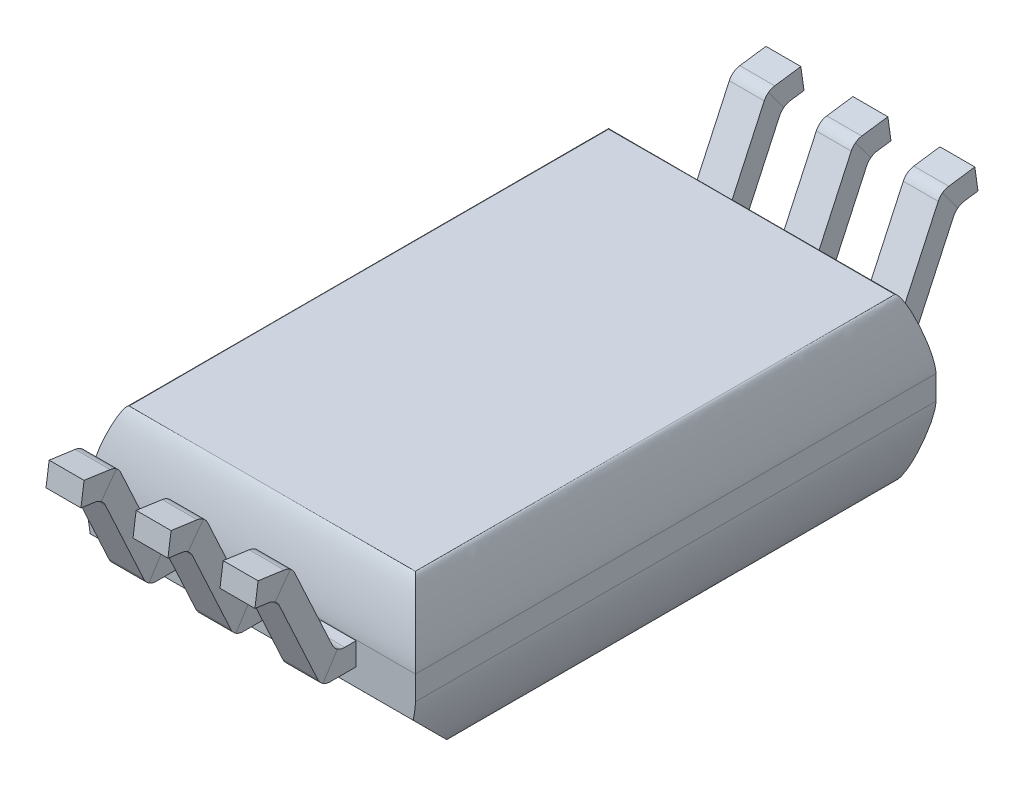
SolidWorks part; units mm, degrees
ref_plane "Front Plane" through (0, 0, 0) normal (0, 0, 1) x (1, 0, 0)
ref_plane "Top Plane" through (0, 0, 0) normal (0, 1, 0) x (1, 0, 0)
ref_plane "Right Plane" through (0, 0, 0) normal (1, 0, 0) x (0, 0, -1)
sketch "Sketch1" plane through (0, 0, 0) normal (0, 1, 0) x (1, 0, 0)
  line L1 (-2.39, -3.8) -> (2.39, -3.8)
  line L2 (-2.39, -3.8) -> (-2.39, 3.8)
  line L3 (-2.39, 3.8) -> (2.39, 3.8)
  line L4 (2.39, -3.8) -> (2.39, 3.8)
  line L5 (-2.39, -3.8) -> (2.39, 3.8) construction
  line L6 (-2.39, 3.8) -> (2.39, -3.8) construction
  point P0 (0, 0)
  dimension "D1" = 4.78
  dimension "D2" = 7.6
sketch "Sketch2" plane through (0, 0, 0) normal (1, 0, 0) x (0, 0, -1)
  line L1 (-3.8, -0.3) -> (3.8, -0.3)
  line L2 (-3.8, -0.3) -> (-3.8, -2.65)
  line L3 (-3.8, -2.65) -> (3.8, -2.65)
  line L4 (3.8, -0.3) -> (3.8, -2.65)
  line L5 (-3.8, -0.3) -> (3.8, -2.65) construction
  line L6 (-3.8, -2.65) -> (3.8, -0.3) construction
  line L8 (3.8, 0) -> (-3.8, 0) construction
  point P0 (0, -1.475)
  dimension "D1" = 2.35
  dimension "D2" = 0.3
extrude "Boss-Extrude1" add sketch "Sketch2" along normal up to vertex (2.39 mm away) and the other way up to vertex (2.39 mm away) up to point (2.39, 0, -3.8) other way up to point (-2.39, 0, -3.8)
sketch "Sketch11" plane through (0, 0, 0) normal (1, 0, 0) x (0, 0, -1)
  line L0 (3.8, -1.475) -> (4.2, -1.475)
  line L1 (3.8, -2.65) -> (3.8, -0.3) construction
  line L2 (4.2, -1.475) -> (4.855, -0.0562)
  line L3 (4.855, -0.0562) -> (5.255, 0)
  line L4 (3.8, 0) -> (-3.8, 0) construction
  dimension "D1" = 8
  dimension "D2" = 0.4
  dimension "D3" = 0.4
  dimension "D4" = 5.255
sketch "Sketch13" plane through (0, 0, -3.8) normal (0, 0, -1) x (-1, 0, 0)
  line L1 (0.255, -1.31) -> (-0.255, -1.31)
  line L2 (0.255, -1.31) -> (0.255, -1.64)
  line L3 (0.255, -1.64) -> (-0.255, -1.64)
  line L4 (-0.255, -1.31) -> (-0.255, -1.64)
  line L5 (0.255, -1.31) -> (-0.255, -1.64) construction
  line L6 (0.255, -1.64) -> (-0.255, -1.31) construction
  point P0 (0, -1.475)
  dimension "D1" = 0.51
  dimension "D2" = 0.33
sweep "Sweep2" add profiles "Sketch13" path "Sketch11"
pattern_linear "LPattern1" count 2 spacing 1.27 along (1, 0, 0) count 2 spacing 1.27 along (-1, 0, 0) of "Sweep2" pattern seed only yes
ref_plane "Plane1" through (0, 0, 0) normal (0, 0, 1) x (1, 0, 0)
mirror "Mirror1" about plane through (0, 0, 0) normal (0, 0, 1) of "LPattern1"
chamfer "Chamfer2" distance 0.75 1 edges at (0, -2.65, 3.8)
fillet "Fillet4" radius 0.3 4 edges at (2.39, -0.3, 0) (0, -0.3, -3.8) (0, -0.3, 3.8) (-2.39, -0.3, 0) second distance 1 conic rho 0.2 first distance on face at (0, -0.3, 0)
fillet "Fillet5" radius 0.3 3 edges at (2.39, -2.65, -0.375) (0, -2.65, -3.8) (-2.39, -2.65, -0.375) second distance 1 conic rho 0.2 first distance on face at (0, -2.65, -0.375)
sketch "Sketch15" plane through (0, -2.65, 0) normal (0, -1, 0) x (1, 0, 0)
  line L0 (2.09, -3.5) -> (2.09, 3.05) construction
  line L2 (2.09, 3.05) -> (-2.09, 3.05) construction
  circle A0 centre (1.59, 2.55) radius 0.25
  dimension "D3" = 0.5
  dimension "D1" = 0.5
  dimension "D2" = 0.5
extrude "Cut-Extrude1" cut sketch "Sketch15" against normal blind 0.1
fillet "Fillet6" radius 0.2 24 edges at (-1.27, 0.0947, -4.7429) (-1.27, -1.31, -4.0944) (0, -1.31, -4.0944) (0, 0.0947, -4.7429) (1.27, -1.31, -4.0944) (1.27, 0.0947, -4.7429) (1.27, -0.2071, -4.9671) (1.27, -1.64, -4.3056) (0, -1.64, -4.3056) (0, -0.2071, -4.9671) (-1.27, -0.2071, -4.9671) (-1.27, -1.64, -4.3056) (1.27, -1.64, 4.3056) (0, -1.64, 4.3056) (-1.27, -1.64, 4.3056) (-1.27, -0.2071, 4.9671) (0, -0.2071, 4.9671) (1.27, -0.2071, 4.9671) (1.27, -1.31, 4.0944) (1.27, 0.0947, 4.7429) (0, 0.0947, 4.7429) (0, -1.31, 4.0944) (-1.27, -1.31, 4.0944) (-1.27, 0.0947, 4.7429)
